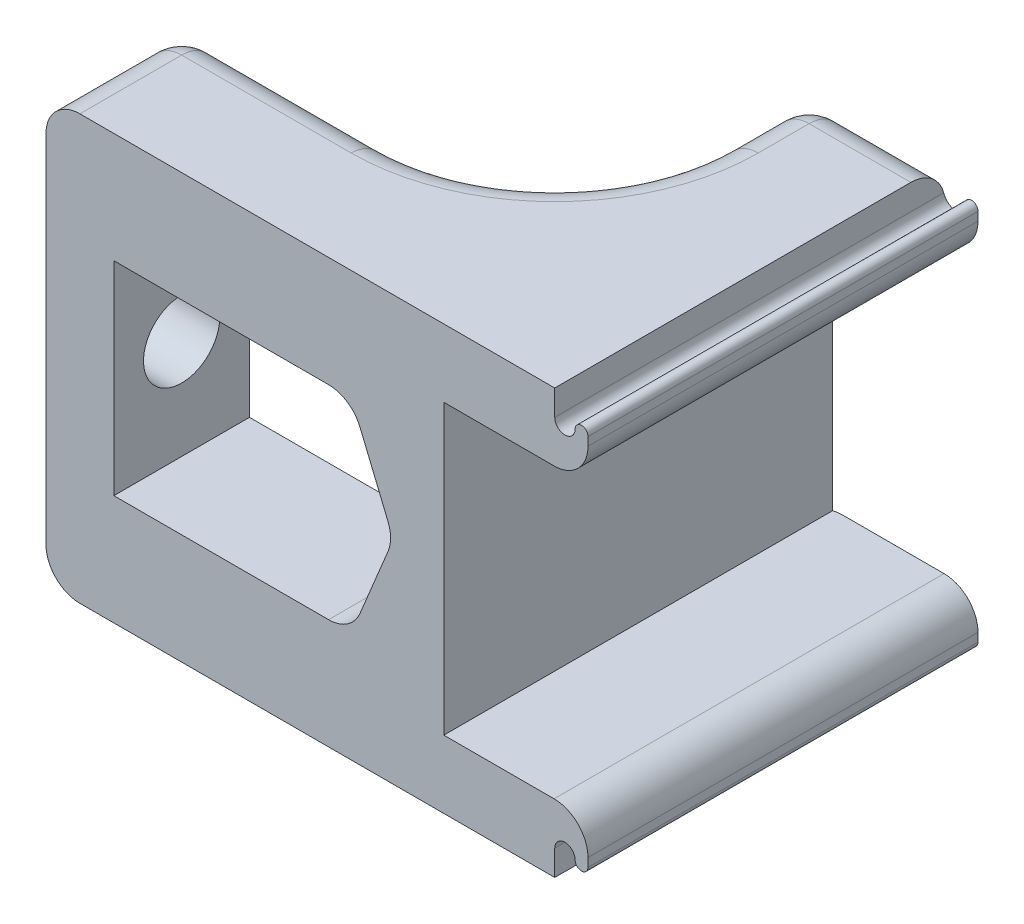
SolidWorks part; units mm, degrees
ref_plane "Přední rovina" through (0, 0, 0) normal (0, 0, 1) x (1, 0, 0)
ref_plane "Horní rovina" through (0, 0, 0) normal (0, 1, 0) x (1, 0, 0)
ref_plane "Pravá rovina" through (0, 0, 0) normal (1, 0, 0) x (0, 0, -1)
sketch "Skica1" plane through (0, 0, 0) normal (0, 0, 1) x (1, 0, 0)
  line L0 (0, 0) -> (0, 25)
  line L1 (0, 25) -> (30, 25)
  line L2 (30, 25) -> (30, 0)
  line L3 (30, 0) -> (0, 0)
  line L4 (4, 18.5) -> (4, 6.5)
  line L5 (4, 6.5) -> (18, 6.5)
  line L6 (18, 6.5) -> (20.4853, 12.5)
  line L7 (20.4853, 12.5) -> (18, 18.5)
  line L8 (18, 18.5) -> (4, 18.5)
  point P7 (4, 12.5)
  point P11 (0, 12.5)
  dimension "D1" = 25
  dimension "D2" = 12
  dimension "D3" = 4
  dimension "D4" = 14
  dimension "D5" = 14
  dimension "D6" = 135
  dimension "D7" = 30
extrude "Přidat vysunutím1" add sketch "Skica1" along normal blind 8
sketch "Skica2" plane through (0, 0, 0) normal (-1, 0, 0) x (0, 0, 1)
  line L0 (8, 25) -> (0, 25) construction
  line L1 (0, 25) -> (0, 0) construction
  circle A0 centre (4, 12.5) radius 2.25
  point P5 (4, 25)
  point P9 (0, 12.5)
  dimension "D1" = 4.5
extrude "Odebrat vysunutím1" cut sketch "Skica2" against normal blind 8
sketch "Skica3" plane through (0, 0, 0) normal (0, 0, -1) x (-1, 0, 0)
  line L0 (0, 0) -> (-30, 0) construction
  line L1 (-30, 25) -> (-22, 25)
  line L2 (-30, 25) -> (-30, 0)
  line L3 (-30, 0) -> (-22, 0)
  line L4 (-22, 25) -> (-22, 0)
  line L5 (-4, 18.5) -> (-4, 6.5) construction
  dimension "D1" = 18
extrude "Přidat vysunutím3" add sketch "Skica3" along normal blind 15
fillet "Zaoblit3" radius 10 1 edges at (22, 12.5, 0)
fillet "Zaoblit5" radius 2 1 edges at (0, 12.5, 0)
fillet "Zaoblit6" radius 2 5 edges at (0, 0, 5) (0.5858, 0, 0.5858) (7, 0, 0) (19.0711, 0, -2.9289) (22, 0, -12.5)
fillet "Zaoblit7" radius 2 5 edges at (0, 25, 5) (0.5858, 25, 0.5858) (7, 25, 0) (19.0711, 25, -2.9289) (22, 25, -12.5)
sketch "Skica6" plane through (0, 0, -15) normal (0, 0, -1) x (-1, 0, 0)
  line L0 (-30, 23.5) -> (-30, 1.5)
  line L1 (-30, 25) -> (-30, 0) construction
  line L2 (-31.96, 23.5) -> (-31.96, 1.5)
  arc A0 (-30, 23.5) -> (-31.2, 23.5) centre (-30.6, 23.5) cw
  arc A1 (-31.2, 23.5) -> (-31.96, 23.5) centre (-31.58, 23.5) ccw
  arc A2 (-30, 1.5) -> (-31.2, 1.5) centre (-30.6, 1.5) ccw
  arc A3 (-31.2, 1.5) -> (-31.96, 1.5) centre (-31.58, 1.5) cw
  dimension "D1" = 1.5
  dimension "D3" = 0.6
  dimension "D4" = 0.38
  dimension "D5" = 0.6
  dimension "D6" = 0.38
  dimension "D2" = 1.5
extrude "Přidat vysunutím6" add sketch "Skica6" against normal blind 23
fillet "Zaoblit12" radius 2 5 edges at (27, 0, -15) (22.5858, 0.5858, -15) (27, 25, -15) (22.5858, 24.4142, -15) (22, 12.5, -15)
fillet "Zaoblit13" radius 2 1 edges at (20.4853, 12.5, 1.6458)
fillet "Zaoblit14" radius 2 1 edges at (18, 18.5, 3)
fillet "Zaoblit15" radius 2 1 edges at (18, 6.5, 3)
sketch "Skica7" plane through (31.96, 0, 0) normal (1, 0, 0) x (0, 0, -1)
  line L0 (-8, 23.5) -> (-8, 1.5) construction
  line L1 (-8, 21) -> (15, 21)
  line L2 (-8, 21) -> (-8, 4)
  line L3 (-8, 4) -> (15, 4)
  line L4 (15, 21) -> (15, 4)
  line L5 (-8, 23.5) -> (15, 23.5) construction
  dimension "D1" = 23
  dimension "D2" = 0
  dimension "D3" = 17
  dimension "D4" = 2.5
extrude "Odebrat vysunutím4" cut sketch "Skica7" against normal blind 8.5
fillet "Zaoblit18" radius 2 1 edges at (31.96, 21, -3.5)
fillet "Zaoblit19" radius 2 1 edges at (31.96, 4, -3.5)
